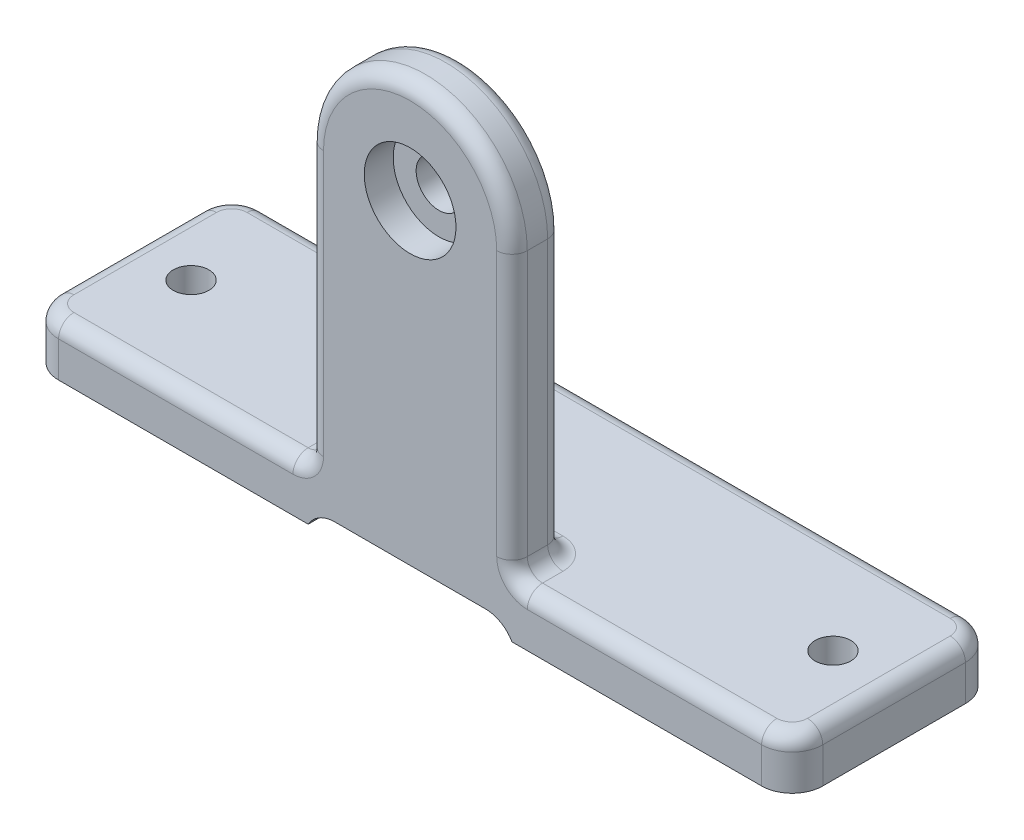
SolidWorks part; units mm, degrees
ref_plane "Front Plane" through (0, 0, 0) normal (0, 0, 1) x (1, 0, 0)
ref_plane "Top Plane" through (0, 0, 0) normal (0, 1, 0) x (1, 0, 0)
ref_plane "Right Plane" through (0, 0, 0) normal (1, 0, 0) x (0, 0, -1)
sketch "Sketch1" plane through (0, 0, 0) normal (0, 1, 0) x (1, 0, 0)
  line L1 (0, 0) -> (150, 0)
  line L2 (0, 0) -> (0, 40)
  line L3 (0, 40) -> (150, 40)
  line L4 (150, 0) -> (150, 40)
  dimension "D1" = 150
  dimension "D2" = 40
extrude "Base Plate" add sketch "Sketch1" along normal blind 10
sketch "Sketch2" plane through (0, 0, 0) normal (0, 0, 1) x (1, 0, 0)
  line L0 (55, 0) -> (55, 65)
  line L1 (0, 0) -> (150, 0) construction
  line L2 (95, 65) -> (95, 0)
  line L3 (95, 0) -> (55, 0)
  line L4 (0, 10) -> (0, 0) construction
  arc A0 (55, 65) -> (95, 65) centre (75, 65) cw
  dimension "D1" = 20
  dimension "D2" = 75
  dimension "D3" = 65
extrude "Vert Boss" add sketch "Sketch2" against normal blind 10
sketch "Sketch5" plane through (0, 0, 0) normal (0, 0, 1) x (1, 0, 0)
  line L0 (0, 0) -> (150, 0) construction
  line L1 (55, 0) -> (95, 0)
  line L2 (55, 0) -> (55, 3)
  line L3 (55, 3) -> (95, 3)
  line L4 (95, 0) -> (95, 3)
  line L5 (55, 65) -> (55, 10) construction
  line L6 (95, 10) -> (95, 65) construction
  dimension "D1" = 3
extrude "Slot" cut sketch "Sketch5" against normal through all
hole_wizard "Ø7.0 (7) Diameter Hole1" positions "Sketch9" profile "Sketch8" hole size "Ø7.0" standard "Ansi Metric" end condition through all
sketch "Sketch9" plane through (0, 10, 0) normal (0, 1, 0) x (-1, 0, 0)
  line L0 (-150, 0) -> (-150, -40) construction
  line L1 (-150, -40) -> (0, -40) construction
  line L2 (0, -40) -> (0, 0) construction
  point P0 (-138, -20)
  point P1 (-12, -20)
  dimension "D1" = 12
  dimension "D2" = 20
  dimension "D3" = 12
sketch "Sketch8" plane through (138, 10, -20) normal (1, 0, 0) x (0, 0, 1)
  line L0 (0, 0) -> (0, 10)
  line L1 (0, 10) -> (3.5, 10)
  line L2 (3.5, 10) -> (3.5, 0)
  line L5 (3.5, 0) -> (0, 0)
  line L11 (0, -6.35) -> (0, 107.95) construction
  dimension "Thru Hole Dia." = 7
  dimension "Thru Hole Depth" = 10
hole_wizard "CBORE for M8 Hex Head Bolt1" positions "Sketch4" profile "Sketch3" counterbore size "M8" standard "Ansi Metric" end condition through all
sketch "Sketch4" plane through (0, 0, 0) normal (0, 0, 1) x (1, 0, 0)
  point P0 (75, 65)
sketch "Sketch3" plane through (75, 65, 0) normal (1, 0, 0) x (0, -1, 0)
  line L0 (0, 0) -> (0, 40)
  line L1 (0, 40) -> (4.5, 40)
  line L3 (4.5, 40) -> (4.5, 5.68)
  line L4 (4.5, 5.68) -> (9.005, 5.68)
  line L5 (9.005, 5.68) -> (9.005, 0)
  line L7 (9.005, 0) -> (0, 0)
  line L11 (0, -6.35) -> (0, 107.95) construction
  dimension "Thru Hole Dia." = 9
  dimension "Thru Hole Depth" = 40
  dimension "C'Bore Dia." = 18.01
  dimension "C'Bore Depth" = 5.68
fillet "Fillet1" radius 6 6 edges at (95, 3, -20) (55, 3, -20) (0, 5, 0) (0, 5, -40) (150, 5, -40) (150, 5, 0)
fillet "Fillet2" radius 3 18 edges at (1.7574, 10, -38.2426) (0, 10, -20) (75, 10, -40) (1.7574, 10, -1.7574) (148.2426, 10, -38.2426) (30.5, 10, 0) (150, 10, -20) (55, 10, -5) (148.2426, 10, -1.7574) (75, 10, -10) (119.5, 10, 0) (95, 37.5, -10) (55, 37.5, -10) (95, 37.5, 0) (55, 37.5, 0) (95, 10, -5) (75, 85, -10) (75, 85, 0)
